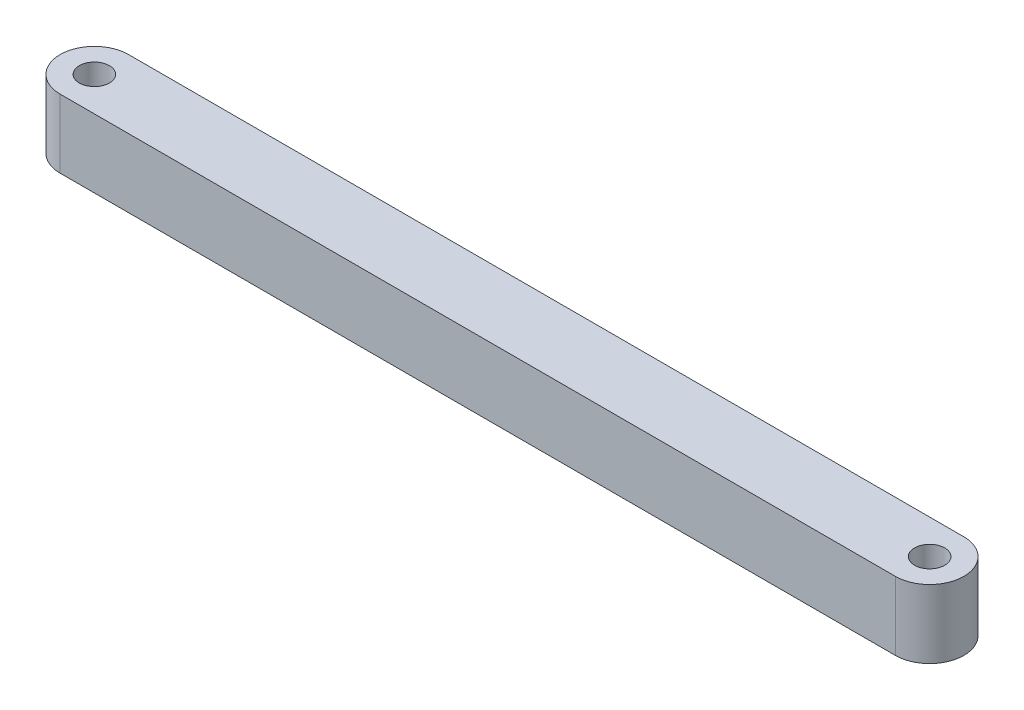
SolidWorks part; units mm, degrees
ref_plane "Front Plane" through (0, 0, 0) normal (0, 0, 1) x (1, 0, 0)
ref_plane "Top Plane" through (0, 0, 0) normal (0, 1, 0) x (1, 0, 0)
ref_plane "Right Plane" through (0, 0, 0) normal (1, 0, 0) x (0, 0, -1)
sketch "Sketch1" plane through (0, 0, 0) normal (0, 1, 0) x (1, 0, 0)
  line L0 (-58.7, 2.5) -> (2.27, 2.5)
  line L1 (-58.7, -2.5) -> (2.27, -2.5)
  arc A0 (-58.7, 2.5) -> (-58.7, -2.5) centre (-58.7, 0) ccw
  arc A1 (2.27, -2.5) -> (2.27, 2.5) centre (2.27, 0) ccw
  circle A2 centre (2.27, 0) radius 1.1
  circle A3 centre (-58.7, 0) radius 1.1
  point P4 (0, 0)
  dimension "D1" = 5
  dimension "D2" = 5
  dimension "D3" = 2.2
  dimension "D4" = 2.2
extrude "Boss-Extrude1" add sketch "Sketch1" along normal blind 5
